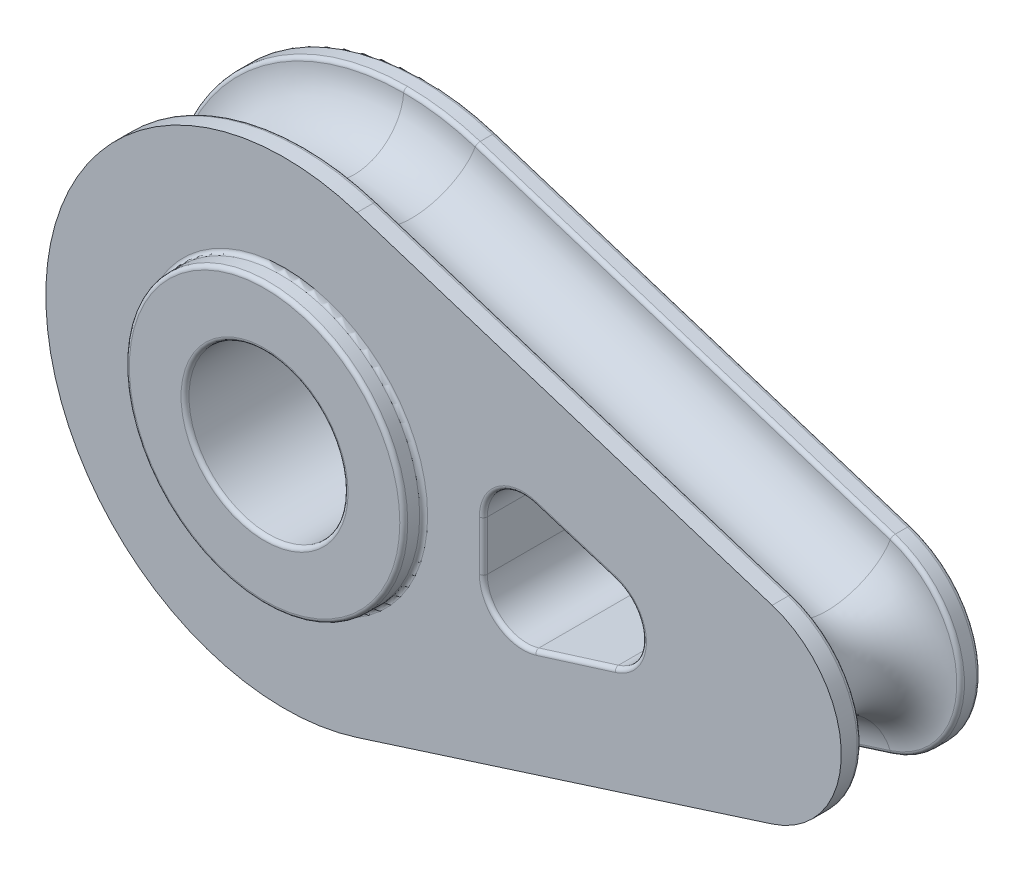
SolidWorks part; units mm, degrees
note: The reader was unsure of these and kept them because the rebuilt part matched: shared geometry of "Sketch1<3>".
ref_plane "Front Plane" through (0, 0, 0) normal (0, 0, 1) x (1, 0, 0)
ref_plane "Top Plane" through (0, 0, 0) normal (0, 1, 0) x (1, 0, 0)
ref_plane "Right Plane" through (0, 0, 0) normal (1, 0, 0) x (0, 0, -1)
sketch "Sketch1" plane through (0, 0, 0) normal (0, 0, 1) x (1, 0, 0)
  line L0 (46.3826, -145.1703) -> (311.4261, -60.4876)
  line L1 (0, 0) -> (292.1, 0) construction
  line L2 (210.7762, -24.2438) -> (159.9762, -40.1188)
  line L3 (210.7762, 24.2438) -> (159.9762, 40.1188)
  line L4 (127, 15.875) -> (127, -15.875)
  line L5 (46.3826, 145.1703) -> (311.4261, 60.4876)
  arc A0 (46.3826, 145.1703) -> (46.3826, -145.1703) centre (0, 0) ccw
  arc A1 (311.4261, -60.4876) -> (311.4261, 60.4876) centre (292.1, 0) ccw
  circle A2 centre (0, 0) radius 88.9
  circle A3 centre (0, 0) radius 50.8
  arc A7 (210.7762, -24.2438) -> (210.7762, 24.2438) centre (203.2, 0) ccw
  arc A8 (127, -15.875) -> (159.9762, -40.1188) centre (152.4, -15.875) ccw
  arc A9 (127, 15.875) -> (159.9762, 40.1188) centre (152.4, 15.875) cw
  dimension "D1" = 127
  dimension "D2" = 304.8
  dimension "D3" = 292.1
  dimension "D4" = 177.8
  dimension "D5" = 101.6
  dimension "D6" = 50.8
  dimension "D7" = 50.8
  dimension "D11" = 31.75
  dimension "D10" = 50.8
  dimension "D8" = 88.9
  dimension "D9" = 50.8
extrude "Boss-Extrude1" add sketch "Sketch1" along normal mid plane 88.9 contours L0 A1 L5 A0 A2
extrude "Boss-Extrude2" add sketch "Sketch1<3>" along normal mid plane 114.3 contours A2 A3
sketch "Sketch1<3>" plane through (0, 0, 0) normal (0, 0, 1) x (1, 0, 0) same geometry as "Sketch1"
sketch "Sketch3" plane through (0, 0, 0) normal (0, 0, 1) x (1, 0, 0)
  line L0 (46.3826, -145.1703) -> (311.4261, -60.4876) construction
  line L1 (46.3826, 145.1703) -> (311.4261, 60.4876) construction
  line L2 (46.3826, -145.1703) -> (311.4261, -60.4876)
  line L3 (46.3826, 145.1703) -> (311.4261, 60.4876)
  arc A0 (46.3826, 145.1703) -> (46.3826, -145.1703) centre (0, 0) ccw construction
  arc A1 (311.4261, -60.4876) -> (311.4261, 60.4876) centre (292.1, 0) ccw construction
  arc A2 (46.3826, 145.1703) -> (46.3826, -145.1703) centre (0, 0) ccw
  arc A3 (311.4261, -60.4876) -> (311.4261, 60.4876) centre (292.1, 0) ccw
curve "CompCurve1"
sketch "Sketch5" plane through (0, 0, 0) normal (1, 0, 0) x (0, 0, -1)
  line L0 (0, 0) -> (0, 260.2866) construction
  line L2 (44.45, 152.4) -> (-44.45, 152.4) construction
  circle A0 centre (0, 152.4) radius 31.75
  dimension "D1" = 63.5
sweep "Cut-Sweep2" cut profiles "Sketch5" path "CompCurve1"
fillet "Fillet1" radius 2.54 32 edges at (88.9, 0, 44.45) (50.8, 0, -57.15) (50.8, 0, 57.15) (88.9, 0, 57.15) (228.6, 0, -44.45) (185.3762, -32.1813, -44.45) (137.3547, -36.3395, -44.45) (127, 0, -44.45) (137.3547, 36.3395, -44.45) (355.6, 0, 31.75) (355.6, 0, -31.75) (178.9043, -102.829, 31.75) (178.9043, -102.829, -31.75) (-150.5817, -23.4713, 31.75) (-150.5817, -23.4713, -31.75) (23.4713, 150.5817, 31.75) (23.4713, 150.5817, -31.75) (-152.4, 0, -44.45) (178.9043, -102.829, -44.45) (355.6, 0, -44.45) (185.3762, -32.1813, 44.45) (228.6, 0, 44.45) (185.3762, 32.1813, 44.45) (137.3547, 36.3395, 44.45) (127, 0, 44.45) (137.3547, -36.3395, 44.45) (185.3762, 32.1813, -44.45) (178.9043, 102.829, 31.75) (178.9043, 102.829, -31.75) (178.9043, 102.829, -44.45) (88.9, 0, -57.15) (88.9, 0, -44.45)
